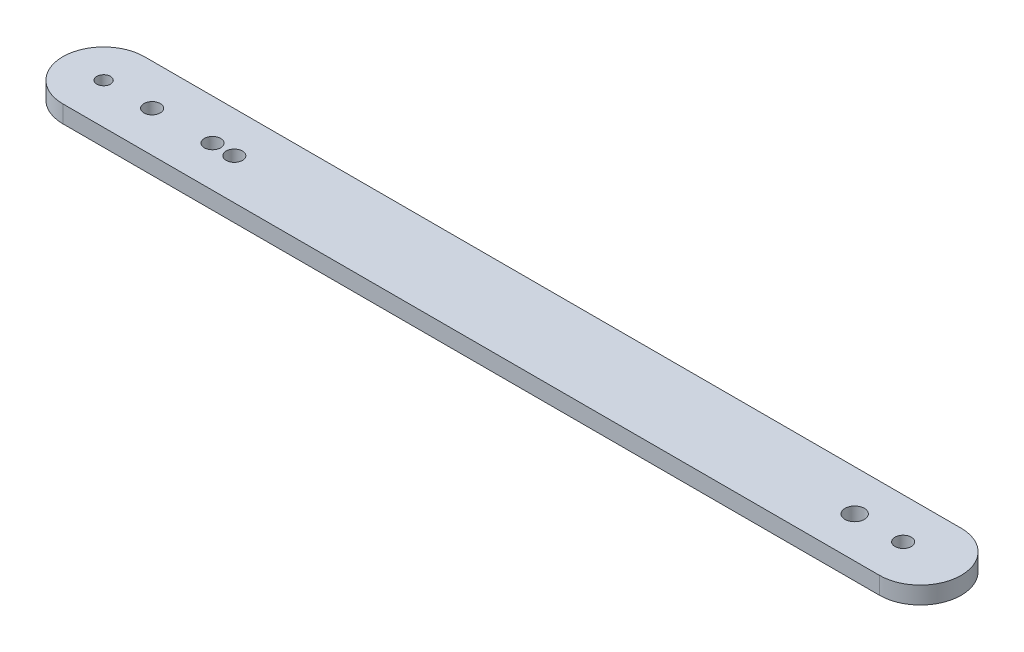
SolidWorks part; units mm, degrees
ref_plane "Front Plane" through (0, 0, 0) normal (0, 0, 1) x (1, 0, 0)
ref_plane "Top Plane" through (0, 0, 0) normal (0, 1, 0) x (1, 0, 0)
ref_plane "Right Plane" through (0, 0, 0) normal (1, 0, 0) x (0, 0, -1)
sketch "Sketch1" plane through (0, 0, 0) normal (0, 1, 0) x (1, 0, 0)
  line L0 (-82.5, 0) -> (82.5, 0) construction
  line L1 (-75, 7.5) -> (75, 7.5)
  line L3 (-75, -7.5) -> (75, -7.5)
  line L5 (-75, 7.5) -> (75, -7.5) construction
  line L6 (-75, -7.5) -> (75, 7.5) construction
  arc A0 (-75, 7.5) -> (-75, -7.5) centre (-75, 0) ccw
  arc A1 (75, -7.5) -> (75, 7.5) centre (75, 0) ccw
  circle A6 centre (-75, 0) radius 1.25
  circle A7 centre (-66.1, 0) radius 1.5
  circle A8 centre (-55, 0) radius 1.5
  circle A10 centre (-51, 0) radius 1.5
  circle A11 centre (71.8389, 0) radius 1.5
  circle A12 centre (62.9389, 0) radius 1.7758
  point P0 (0, 0)
  dimension "D1" = 2.5
  dimension "D6" = 3
  dimension "D2" = 11.1
  dimension "D3" = 4
  dimension "D4" = 15
  dimension "D5" = 150
  dimension "D7" = 8.9
  dimension "D8" = 8.9
extrude "Boss-Extrude1" add sketch "Sketch1" along normal blind 3.175
